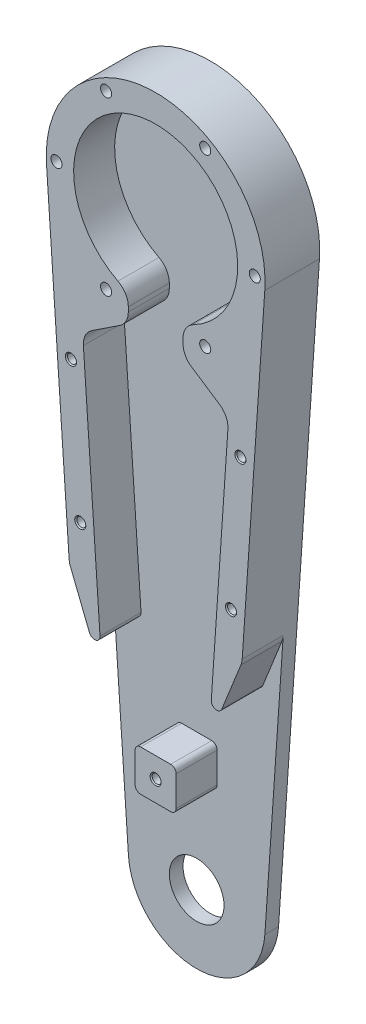
SolidWorks part; units mm, degrees
note: The reader was unsure of these and kept them because the rebuilt part matched: shared geometry of "Sketch1<3>".
ref_plane "Front Plane" through (0, 0, 0) normal (0, 0, 1) x (1, 0, 0)
ref_plane "Top Plane" through (0, 0, 0) normal (0, 1, 0) x (1, 0, 0)
ref_plane "Right Plane" through (0, 0, 0) normal (1, 0, 0) x (0, 0, -1)
sketch "Sketch1" plane through (0, 0, 0) normal (0, 0, 1) x (1, 0, 0)
  line L0 (-1000, 0) -> (49000, 0) construction
  line L1 (0, -1000) -> (0, 49000) construction
  circle A0 centre (0, 0) radius 40
  circle A1 centre (0, 0) radius 30
  circle A2 centre (0, 0) radius 36.25 construction
  point P4 (0, 36.25)
  dimension "D1" = 80
  dimension "D2" = 60
  dimension "D3" = 72.5
extrude "Boss-Extrude1" add sketch "Sketch1" against normal blind 5
hole_wizard "M4x0.7 Tapped Hole1" positions "Sketch7" profile "Sketch8" tap size "M4x0.7" standard "ANSI Metric" end condition through all
sketch "Sketch7" plane through (0, 0, 0) normal (0, 0, 1) x (1, 0, 0)
  line L0 (0, 0) -> (36.25, 0) construction
  circle A0 centre (0, 0) radius 36.25 construction
  point P9 (36.25, 0)
  point P15 (0, 0)
cosmetic thread "Hole Thread1" parameters "D2"=4
sketch "Sketch8" plane through (36.25, 0, 0) normal (1, 0, 0) x (0, -1, 0)
  line L0 (0, 0) -> (0, 5)
  line L1 (0, 5) -> (1.65, 5)
  line L2 (1.65, 5) -> (1.65, 0.375)
  line L3 (1.65, 0.375) -> (2.025, 0)
  line L5 (2.025, 0) -> (0, 0)
  line L6 (-1.65, 0.375) -> (-2.025, 0) construction
  line L11 (0, -6.35) -> (0, 107.95) construction
  dimension "Thru Tap Drill Dia." = 3.3
  dimension "Thru Tap Drill Depth" = 5
  dimension "Near C'Sink Dia." = 4.05
  dimension "Near C'Sink Angle" = 90
sketch "Sketch9" plane through (0, 0, 0) normal (1, 0, 0) x (0, 0, -1)
  line L0 (-1000, 0) -> (49000, 0) construction
pattern_circular "CirPattern1" count 6 over 360 about axis through (0, 0, 0) along (0, 0, 1) of "M4x0.7 Tapped Hole1"
cosmetic thread "Hole Thread2" parameters "D2"=4
cosmetic thread "Hole Thread3" parameters "D2"=4
cosmetic thread "Hole Thread4" parameters "D2"=4
cosmetic thread "Hole Thread5" parameters "D2"=4
cosmetic thread "Hole Thread6" parameters "D2"=4
cosmetic thread "Hole Thread7" parameters "D2"=4
cosmetic thread "Hole Thread8" parameters "D2"=4
cosmetic thread "Hole Thread9" parameters "D2"=4
cosmetic thread "Hole Thread10" parameters "D2"=4
cosmetic thread "Hole Thread11" parameters "D2"=4
cosmetic thread "Hole Thread12" parameters "D2"=4
sketch "Sketch14" plane through (0, 0, 0) normal (0, 0, 1) x (1, 0, 0)
  line L0 (-1000, 0) -> (49000, 0) construction
  line L1 (0, -1000) -> (0, 49000) construction
  line L2 (-1000, -220) -> (49000, -220) construction
  line L3 (-39.9069, -2.7273) -> (-24.9418, -221.7045)
  line L4 (39.9069, -2.7273) -> (24.9418, -221.7045)
  circle A0 centre (0, -220) radius 25
  circle A1 centre (0, 0) radius 40 construction
  circle A2 centre (0, 0) radius 40
  circle A3 centre (0, -220) radius 10
  dimension "D2" = 50
  dimension "D3" = 20
  dimension "D1" = 220
extrude "Boss-Extrude5" add sketch "Sketch14" against normal blind 5 contours A2 L3 A0 L4 | A0
sketch "Sketch15" plane through (0, 0, 0) normal (0, 0, 1) x (1, 0, 0)
  line L0 (0, -1000) -> (0, 49000) construction
  line L1 (10, -28.2843) -> (10, -38.2843)
  line L2 (-39.9069, -2.7273) -> (-24.9418, -221.7045)
  line L3 (24.9418, -221.7045) -> (39.9069, -2.7273)
  line L4 (-39.9069, -2.7273) -> (-24.9418, -221.7045)
  line L5 (24.9418, -221.7045) -> (39.9069, -2.7273)
  line L6 (10, -38.2843) -> (10, -28.2843)
  line L7 (10, -38.2843) -> (26.7017, -49.2867)
  line L8 (26.7017, -49.2867) -> (19.4771, -155)
  line L9 (7.5, -185) -> (19.4771, -155)
  line L10 (7.5, -170) -> (-7.5, -170)
  line L11 (19.4771, -155) -> (31.5706, -124.7086)
  line L12 (-26.7017, -49.2867) -> (-19.4771, -155)
  line L13 (-10, -38.2843) -> (-26.7017, -49.2867)
  line L14 (-10, -28.2843) -> (-10, -38.2843)
  line L15 (-19.4771, -155) -> (-31.5706, -124.7086)
  line L16 (-7.5, -185) -> (-19.4771, -155)
  line L17 (-7.5, -170) -> (7.5, -170)
  line L18 (-7.5, -170) -> (-7.5, -185)
  line L19 (7.5, -170) -> (7.5, -185)
  line L20 (-7.5, -185) -> (7.5, -185)
  line L22 (0, -201000) -> (0, 249000) construction
  circle A1 centre (0, 0) radius 30 construction
  arc A2 (39.9069, -2.7273) -> (-39.9069, -2.7273) centre (0, 0) ccw
  arc A3 (-24.9418, -221.7045) -> (24.9418, -221.7045) centre (0, -220) ccw
  arc A4 (39.9069, -2.7273) -> (-39.9069, -2.7273) centre (0, 0) ccw
  arc A5 (-24.9418, -221.7045) -> (24.9418, -221.7045) centre (0, -220) ccw
  circle A6 centre (0, 0) radius 30
  point P17 (0, -177.5)
  point P22 (0, -170)
  dimension "D2" = 50
  dimension "D3" = 10
  dimension "D4" = 10
  dimension "D5" = 10
  dimension "D6" = 30
  dimension "D7" = 20
  dimension "D8" = 7.5
  dimension "D9" = 15
  dimension "D10" = 7.5
  dimension "D1" = 0
extrude "Boss-Extrude7" add sketch "Sketch15" along normal blind 15
fillet "Fillet3" radius 2 6 edges at (-7.5, -185, 7.5) (-7.5, -170, 7.5) (7.5, -185, 7.5) (7.5, -170, 7.5) (19.4771, -155, 7.5) (-19.4771, -155, 7.5)
fillet "Fillet4" radius 7 8 edges at (-31.5706, -124.7086, 7.5) (31.5706, -124.7086, 7.5) (26.7017, -49.2867, 7.5) (-26.7017, -49.2867, 7.5) (10, -38.2843, 7.5) (10, -28.2843, 7.5) (-10, -38.2843, 7.5) (-10, -28.2843, 7.5)
sketch "Sketch21" plane through (0, 0, 15) normal (0, 0, 1) x (1, 0, 0)
  line L0 (-1000, -60) -> (49000, -60) construction
  line L1 (-34.9186, -2.3864) -> (-19.9535, -221.3636) construction
  line L2 (-1000, -110) -> (49000, -110) construction
  line L3 (19.9535, -221.3636) -> (34.9186, -2.3864) construction
  line L6 (24.9418, -221.7045) -> (39.9069, -2.7273) construction
  line L7 (-39.9069, -2.7273) -> (-24.9418, -221.7045) construction
  line L8 (24.9418, -221.7045) -> (39.9069, -2.7273) construction
  line L9 (-39.9069, -2.7273) -> (-24.9418, -221.7045) construction
  point P0 (0, -177.5)
  point P5 (0, 0)
  point P8 (0, 0)
  point P17 (-30.9812, -60)
  point P18 (-27.5641, -110)
  point P21 (27.5641, -110)
  point P22 (30.9812, -60)
  dimension "D1" = 50
  dimension "D3" = 60
  dimension "D4" = 5
hole_wizard "M4x0.7 Tapped Hole2" positions "Sketch22" profile "Sketch23" tap size "M4x0.7" standard "ANSI Metric" end condition through all
sketch "Sketch22" plane through (0, 0, 15) normal (0, 0, 1) x (1, 0, 0)
  point P0 (0, -177.5)
  point P10 (-27.5641, -110)
  point P13 (27.5641, -110)
  point P16 (-30.9812, -60)
  point P19 (30.9812, -60)
  point P24 (0, 0)
  point P25 (0, 0)
cosmetic thread "Hole Thread13" parameters "D2"=4
cosmetic thread "Hole Thread14" parameters "D2"=4
cosmetic thread "Hole Thread15" parameters "D2"=4
cosmetic thread "Hole Thread16" parameters "D2"=4
cosmetic thread "Hole Thread17" parameters "D2"=4
sketch "Sketch23" plane through (0, -177.5, 15) normal (1, 0, 0) x (0, -1, 0)
  line L0 (0, 0) -> (0, 20)
  line L1 (0, 20) -> (1.65, 20)
  line L2 (1.65, 20) -> (1.65, 0.375)
  line L3 (1.65, 0.375) -> (2.025, 0)
  line L5 (2.025, 0) -> (0, 0)
  line L6 (-1.65, 0.375) -> (-2.025, 0) construction
  line L11 (0, -6.35) -> (0, 107.95) construction
  dimension "Thru Tap Drill Dia." = 3.3
  dimension "Thru Tap Drill Depth" = 20
  dimension "Near C'Sink Dia." = 4.05
  dimension "Near C'Sink Angle" = 90
extrude "Boss-Extrude8" add sketch "Sketch1<3>" against normal blind 5 contours A1
sketch "Sketch1<3>" plane through (0, 0, 0) normal (0, 0, 1) x (1, 0, 0) same geometry as "Sketch1"
